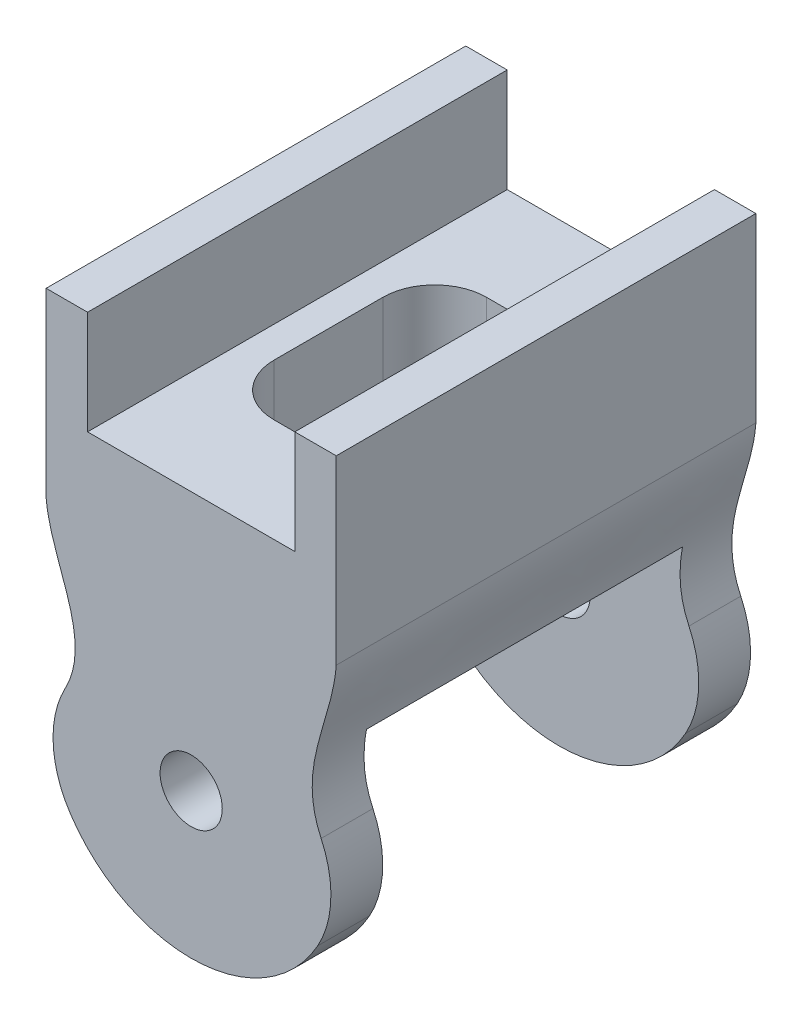
SolidWorks part; units mm, degrees
ref_plane "Plan de face" through (0, 0, 0) normal (0, 0, 1) x (1, 0, 0)
ref_plane "Plan de dessus" through (0, 0, 0) normal (0, 1, 0) x (1, 0, 0)
ref_plane "Plan de droite" through (0, 0, 0) normal (1, 0, 0) x (0, 0, -1)
sketch "Esquisse1" plane through (0, 0, 0) normal (0, 0, 1) x (1, 0, 0)
  line L0 (-14, 0) -> (-14, -35)
  line L1 (0, 0) -> (0, -35) construction
  line L3 (14, -35) -> (14, 0)
  line L4 (-14, 0) -> (14, 0)
  line L6 (-14, 0) -> (-14, 3.841) construction
  line L7 (14, 0) -> (14, 6.0564) construction
  circle A0 centre (0, -35) radius 3
  arc A1 (-14, -35) -> (14, -35) centre (0, -35) ccw
  dimension "D2" = 6
  dimension "D1" = 28
  dimension "D4" = 35
extrude "Boss.-Extru.1" add sketch "Esquisse1" along normal blind 40.5
sketch "Esquisse2" plane through (-14, 0, 0) normal (-1, 0, 0) x (0, 0, 1)
  line L0 (0, 0) -> (0, -35) construction
  line L1 (35.5, -26.4019) -> (5, -26.4019)
  line L2 (35.5, -26.4019) -> (35.5, -51.4019)
  line L3 (35.5, -51.4019) -> (5, -51.4019)
  line L4 (5, -26.4019) -> (5, -51.4019)
  line L5 (40.5, 0) -> (40.5, -35) construction
  dimension "D1" = 5
  dimension "D2" = 5
  dimension "D3" = 25
extrude "Enlèv. mat.-Extru.1" cut sketch "Esquisse2" against normal through all
sketch "Esquisse3" plane through (0, 0, 0) normal (0, 1, 0) x (1, 0, 0)
  line L0 (14, -40.5) -> (14, 0) construction
  line L1 (10, -40.5) -> (-10, -40.5)
  line L2 (10, -40.5) -> (10, 0)
  line L3 (10, 0) -> (-10, 0)
  line L4 (-10, -40.5) -> (-10, 0)
  line L5 (-14, -40.5) -> (-14, 0) construction
  line L6 (14, -40.5) -> (-14, -40.5) construction
  line L7 (14, 0) -> (-14, 0) construction
  dimension "D1" = 4
  dimension "D2" = 4
extrude "Enlèv. mat.-Extru.2" cut sketch "Esquisse3" against normal blind 10
sketch "Esquisse4" plane through (0, -10, 0) normal (0, 1, 0) x (1, 0, 0)
  line L0 (-10, -40.5) -> (10, -40.5) construction
  line L1 (2, -30.5) -> (-2, -30.5)
  line L2 (7, -25.5) -> (7, -15)
  line L3 (2, -10) -> (-2, -10)
  line L4 (-7, -25.5) -> (-7, -15)
  line L5 (10, 0) -> (-10, 0) construction
  line L6 (10, -40.5) -> (10, 0) construction
  line L7 (-10, 0) -> (-10, -40.5) construction
  arc A0 (-7, -15) -> (-2, -10) centre (-2, -15) cw
  arc A1 (7, -15) -> (2, -10) centre (2, -15) ccw
  arc A2 (-7, -25.5) -> (-2, -30.5) centre (-2, -25.5) ccw
  arc A3 (2, -30.5) -> (7, -25.5) centre (2, -25.5) ccw
  dimension "D5" = 5
  dimension "D1" = 10
  dimension "D2" = 10
  dimension "D3" = 3
  dimension "D4" = 3
extrude "Enlèv. mat.-Extru.3" cut sketch "Esquisse4" against normal through all
sketch "Esquisse5" plane through (0, 0, 40.5) normal (0, 0, 1) x (1, 0, 0)
  line L0 (14, -35) -> (14, 0) construction
  line L1 (-14, 0) -> (-14, -35) construction
  line L2 (14, -15.8245) -> (14, -35)
  line L3 (-14, -35) -> (-14, -15.8245)
  spline S0 degree 3 poles (14, -35) (8.5329, -28.2845) (14.5142, -22.3729) (14, -15.8245) knots 0 0 0 0 1 1 1 1
  spline S1 degree 3 poles (-14, -35) (-7.3891, -28.0641) (-14.6192, -22.4228) (-14, -15.8245) knots 0 0 0 0 1 1 1 1
  line M7 (14, -35) -> (14, 0)
extrude "Enlèv. mat.-Extru.4" cut sketch "Esquisse5" against normal through all contours S0 M7 | L3 S1 region at (13.1043, -27.684, 40.5) region at (-12.917, -27.6522, 40.5)
fillet "Congé1" radius 10 4 edges
